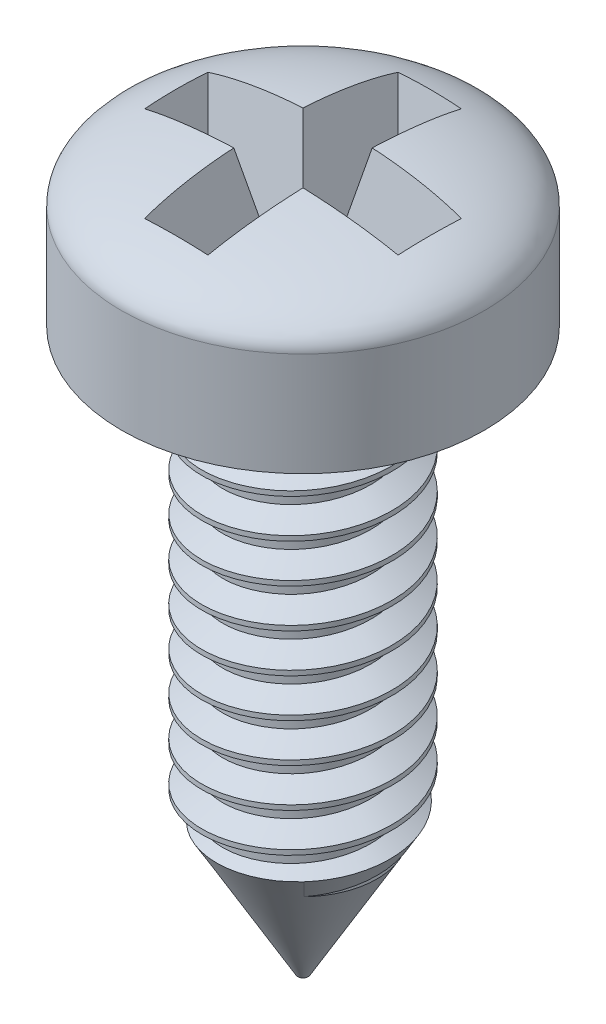
SolidWorks part; units mm, degrees
material "AISI 304"
ref_plane "Plano frontal" through (0, 0, 0) normal (0, 0, 1) x (1, 0, 0)
ref_plane "Plano superior" through (0, 0, 0) normal (0, 1, 0) x (1, 0, 0)
ref_plane "Plano direito" through (0, 0, 0) normal (1, 0, 0) x (0, 0, -1)
sketch "Esboço1" plane through (0, 0, 0) normal (0, 1, 0) x (1, 0, 0)
  circle A0 centre (0, 0) radius 2.1
  dimension "D1" = 4.2
extrude "Ressalto-extrusão1" add sketch "Esboço1" along normal blind 1.8 contours A0
fillet "Filete8" radius 0.6 1 edges at (0, 1.8, 2.1) second distance 2 first distance on face at (0, 1.8, 2.1)
sketch "Esboço3" plane through (0, 1.8, 0) normal (0, 1, 0) x (1, 0, 0)
  line L0 (0.4, 0.4) -> (0.4, 1.5)
  line L7 (-0.4, -1.5) -> (0.4, -1.5)
  line L8 (-0.4, -1.5) -> (-0.4, -0.4)
  line L9 (-0.4, 1.5) -> (0.4, 1.5)
  line L10 (0.4, -1.5) -> (0.4, -0.4)
  line L11 (-0.4, -1.5) -> (0.4, 1.5) construction
  line L12 (-0.4, 1.5) -> (0.4, -1.5) construction
  line L13 (-1.5, -0.4) -> (-0.4, -0.4)
  line L14 (-1.5, -0.4) -> (-1.5, 0.4)
  line L15 (-1.5, 0.4) -> (-0.4, 0.4)
  line L16 (1.5, -0.4) -> (1.5, 0.4)
  line L17 (-1.5, -0.4) -> (1.5, 0.4) construction
  line L18 (-1.5, 0.4) -> (1.5, -0.4) construction
  line L19 (0.4, 0.4) -> (1.5, 0.4)
  line L21 (-0.4, 0.4) -> (-0.4, 1.5)
  line L24 (0.4, -0.4) -> (1.5, -0.4)
  point P0 (0, 0)
  point P5 (0, 0)
  dimension "D1" = 0.8
  dimension "D2" = 0.8
  dimension "D3" = 3
  dimension "D4" = 3
extrude "Corte-extrusão1" cut sketch "Esboço3" against normal blind 1.5
chamfer "Chanfro3" distance 1.48 angle 12 12 edges at (0.4, 0.3, -0.95) (0.95, 0.3, -0.4) (1.5, 0.3, 0) (0.95, 0.3, 0.4) (0.4, 0.3, 0.95) (0, 0.3, 1.5) (-0.4, 0.3, 0.95) (-0.95, 0.3, 0.4) (-1.5, 0.3, 0) (-0.95, 0.3, -0.4) (-0.4, 0.3, -0.95) (0, 0.3, -1.5) first distance on face at (0.4, 1.0204, -0.8125) first distance on face at (0.9524, 1.0069, -0.4) first distance on face at (1.5, 0.9562, 0.1) first distance on face at (0.8125, 1.0204, 0.4) first distance on face at (0.4, 0.9776, 1.0875) first distance on face at (-0.018, 0.9601, 1.5) first distance on face at (-0.4, 1.0204, 0.8125) first distance on face at (-0.9524, 1.0069, 0.4) first distance on face at (-1.5, 0.9562, -0.1) first distance on face at (-0.8125, 1.0204, -0.4) first distance on face at (-0.4, 1.0069, -0.9524) first distance on face at (0.1, 0.9562, -1.5)
sketch "Esboço4" plane through (0, 0, 0) normal (0, -1, 0) x (1, 0, 0)
  circle A0 centre (0, 0) radius 1.1
  dimension "D1" = 2.2
extrude "Ressalto-extrusão2" add sketch "Esboço4" along normal blind 6.5
chamfer "Chanfro4" distance 1.8 angle 30 1 edges at (0, -6.5, -1.1) first distance on face at (0, -6.5, -1.1)
fillet "Filete2" radius 0.2 1 edges at (0, 0, -1.1)
thread "Rosca1" pitch 0.45 method cut profile "Perfil da rosca1" start angle 0, offset 0, length 0, pitch 0.45, diameter 2.2
ref_plane "Plano1" through (-1.1, -0.2, 0) normal (0, 0, 1) x (-1, 0, 0)
sketch "Perfil da rosca1" plane through (-1.1, -0.2, 0) normal (0, 0, 1) x (-1, 0, 0)
  line L0 (0, 0) -> (0, 0.45) construction
  line L11 (0, 0) -> (0, 0.3937)
  line L12 (0, 0.3937) -> (-0.2436, 0.2531)
  line L13 (-0.2436, 0.2531) -> (-0.2436, 0.1406)
  line L15 (-0.2436, 0.1406) -> (0, 0)
  line L17 (-0.2436, 0.1969) -> (0, 0.1969) construction
  point P2 (0, 0)
  dimension "Pitch" = 0.45
  dimension "Profile_Angle" = 60
  dimension "Profile_Land" = 0.1125
  dimension "Profile_Height" = 0.2436
